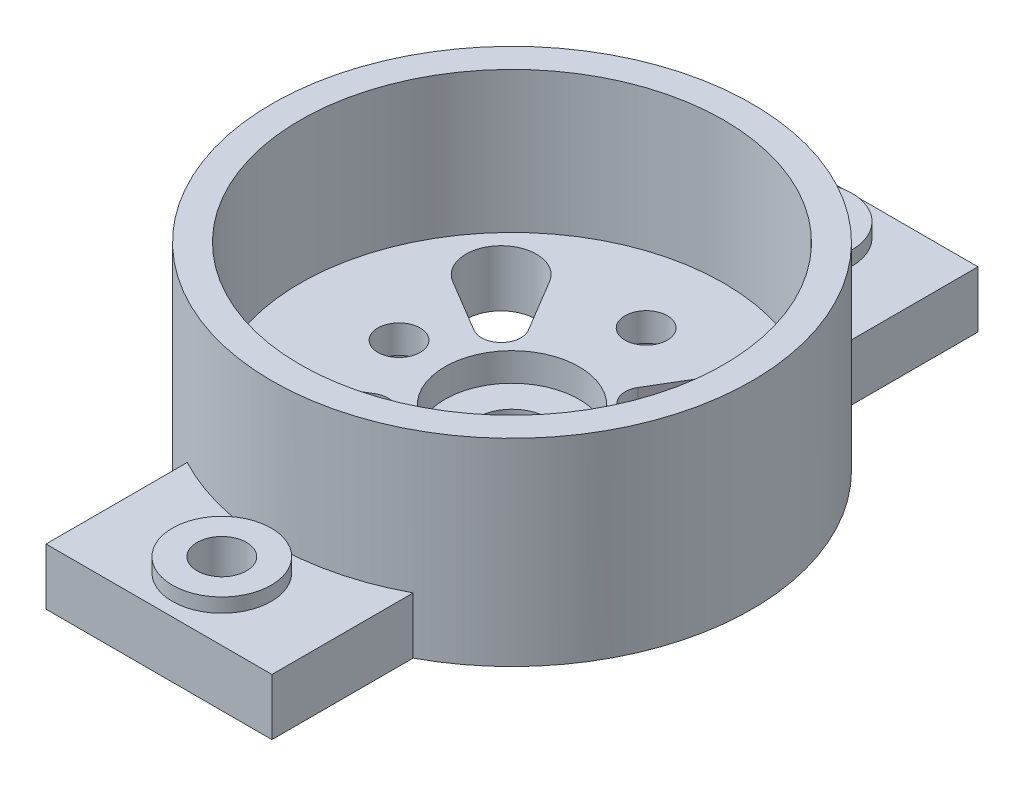
SolidWorks part; units mm, degrees
ref_plane "Piano frontale" through (0, 0, 0) normal (0, 0, 1) x (1, 0, 0)
ref_plane "Piano superiore" through (0, 0, 0) normal (0, 1, 0) x (1, 0, 0)
ref_plane "Piano destro" through (0, 0, 0) normal (1, 0, 0) x (0, 0, -1)
sketch "Schizzo1" plane through (0, 0, 0) normal (0, 1, 0) x (1, 0, 0)
  line L1 (-8, 25) -> (8, 25)
  line L2 (-8, 25) -> (-8, 15)
  line L4 (8, 25) -> (8, 15)
  line L5 (-8, -25) -> (8, -25)
  line L6 (-8, -25) -> (-8, -15)
  line L8 (8, -25) -> (8, -15)
  circle A0 centre (0, 0) radius 17
  dimension "D1" = 34
  dimension "D2" = 16
  dimension "D3" = 10
  dimension "D4" = 10
  dimension "D5" = 16
extrude "Estrusione-Estrusione1" add sketch "Schizzo1" along normal blind 4 contours A0 L6 L5 L8 | A0 | A0 | A0 | A0 | A0 L4 L1 L2 region at (0, 0, -20.6548) region at (0, 0, 0) region at (0, 0, 20.6548)
sketch "Schizzo2" plane through (0, 4, 0) normal (0, 1, 0) x (1, 0, 0)
  circle A0 centre (0, 0) radius 17
  circle A1 centre (0, 0) radius 15
  dimension "D1" = 2
  dimension "D2" = 34
extrude "Estrusione-Estrusione2" add sketch "Schizzo2" along normal blind 10
sketch "Schizzo3" plane through (0, 4, 0) normal (0, 1, 0) x (1, 0, 0)
  line L0 (8, 0) -> (-8, 0) construction
  line L1 (0, -9.5) -> (0, 9.5) construction
  line L2 (0, 15) -> (0, -15) construction
  line L3 (-15, 0) -> (15, 0) construction
  line L4 (-10.6066, 10.6066) -> (10.6066, -10.6066) construction
  line L5 (-10.6066, -10.6066) -> (10.6066, 10.6066) construction
  line L6 (3.7478, -5.6677) -> (5.9855, -9.4137)
  line L7 (5.6677, -3.7478) -> (9.4137, -5.9855)
  line L8 (-3.6441, -6.0515) -> (-5.8818, -9.7976)
  line L9 (-5.564, -4.1317) -> (-9.31, -6.3693)
  line L10 (-5.9478, 3.2603) -> (-9.6939, 5.4979)
  line L11 (-4.028, 5.1801) -> (-6.2656, 8.9262)
  line L12 (3.364, 5.564) -> (5.6016, 9.31)
  line L13 (5.2838, 3.6441) -> (9.0299, 5.8818)
  circle A0 centre (0, 0) radius 2.5
  circle A1 centre (8, 0) radius 1.5
  circle A2 centre (0, 9.5) radius 1.5
  circle A3 centre (-8, 0) radius 1.5
  circle A4 centre (0, -9.5) radius 1.5
  arc A5 (9.4137, -5.9855) -> (5.9855, -9.4137) centre (8.1317, -8.1317) cw
  circle A6 centre (0, 0) radius 7 construction
  circle A7 centre (0, 0) radius 11.5 construction
  arc A8 (3.7478, -5.6677) -> (5.6677, -3.7478) centre (4.9497, -4.9497) cw
  arc A9 (-5.8818, -9.7976) -> (-9.31, -6.3693) centre (-8.028, -8.5156) cw
  arc A10 (-5.564, -4.1317) -> (-3.6441, -6.0515) centre (-4.846, -5.3336) cw
  arc A11 (-9.6939, 5.4979) -> (-6.2656, 8.9262) centre (-8.4119, 7.6442) cw
  arc A12 (-4.028, 5.1801) -> (-5.9478, 3.2603) centre (-5.2299, 4.4622) cw
  arc A13 (5.6016, 9.31) -> (9.0299, 5.8818) centre (7.7479, 8.028) cw
  arc A14 (5.2838, 3.6441) -> (3.364, 5.564) centre (4.5659, 4.846) cw
  point P48 (-0.1401, -0.2438)
  dimension "D1" = 3
  dimension "D6" = 5
  dimension "D7" = 23
  dimension "D8" = 1.4
  dimension "D9" = 2.5
  dimension "D11" = 14
  dimension "D2" = 19
  dimension "D3" = 16
  dimension "D4" = 8
  dimension "D5" = 9.5
  dimension "D10" = 4
extrude "Taglio-Estrusione1" cut sketch "Schizzo3" against normal through all
sketch "Schizzo4" plane through (0, 4, 0) normal (0, 1, 0) x (1, 0, 0)
  circle A0 centre (0, 0) radius 4.75
  dimension "D1" = 9.5
extrude "Taglio-Estrusione2" cut sketch "Schizzo4" against normal blind 2
sketch "Schizzo5" plane through (0, 0, 0) normal (0, -1, 0) x (1, 0, 0)
  circle A0 centre (-8, 0) radius 2.5
  circle A1 centre (0, 9.5) radius 2.5
  circle A2 centre (8, 0) radius 2.5
  circle A3 centre (0, -9.5) radius 2.5
  dimension "D1" = 5
extrude "Taglio-Estrusione3" cut sketch "Schizzo5" against normal blind 2
sketch "Schizzo6" plane through (0, 4, 0) normal (0, 1, 0) x (1, 0, 0)
  line L0 (8, 25) -> (8, 15) construction
  line L1 (-8, -25) -> (-8, -15) construction
  circle A0 centre (0, 20.55) radius 3.5
  arc A1 (8, 15) -> (-8, 15) centre (0, 0) ccw construction
  circle A2 centre (0, -20.55) radius 3.5
  arc A3 (-8, -15) -> (8, -15) centre (0, 0) ccw construction
  point P2 (0, 17)
  point P10 (0, -17)
  dimension "D1" = 7
  dimension "D2" = 3.55
  dimension "D3" = 8
  dimension "D4" = 3.55
  dimension "D5" = 8
extrude "Estrusione-Estrusione8" add sketch "Schizzo6" along normal blind 1
sketch "Schizzo7" plane through (0, 5, 0) normal (0, 1, 0) x (1, 0, 0)
  line L0 (-8, 25) -> (8, 25) construction
  circle A0 centre (0, -20.55) radius 1.75
  circle A1 centre (0, 20.55) radius 1.75
  dimension "D1" = 3.5
extrude "Taglio-Estrusione4" cut sketch "Schizzo7" against normal through all
